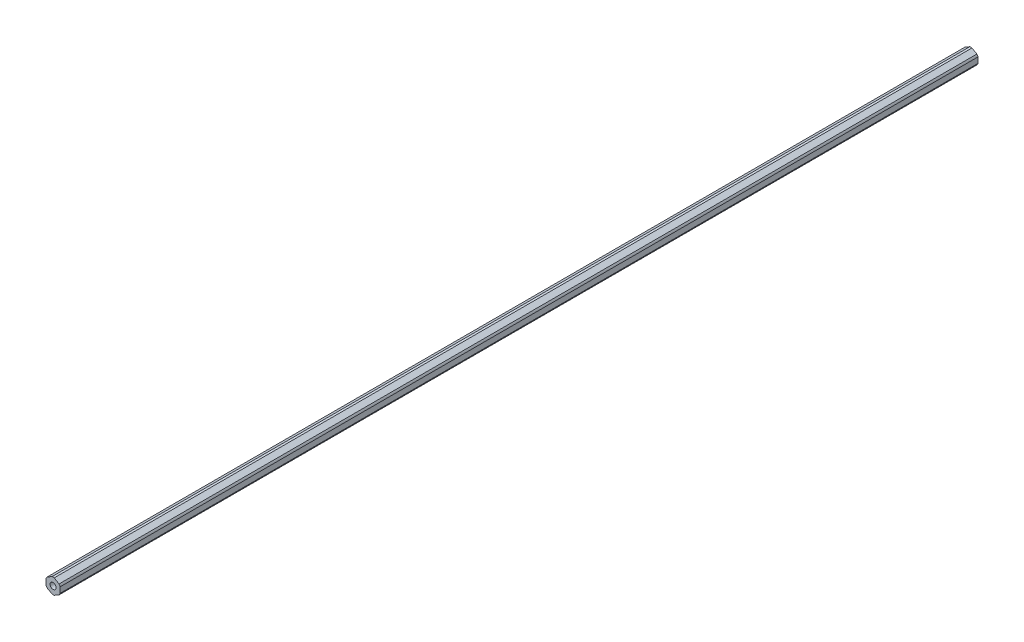
SolidWorks part; units mm, degrees
material "7075-T6 (SN)"
ref_plane "Front Plane" through (0, 0, 0) normal (0, 0, 1) x (1, 0, 0)
ref_plane "Top Plane" through (0, 0, 0) normal (0, 1, 0) x (1, 0, 0)
ref_plane "Right Plane" through (0, 0, 0) normal (1, 0, 0) x (0, 0, -1)
sketch "Sketch2" plane through (0, 0, 0) normal (0, 0, 1) x (1, 0, 0)
  line L1 (0, 5.4993) -> (-4.7625, 2.7496)
  line L2 (-4.7625, 2.7496) -> (-4.7625, -2.7496)
  line L3 (-4.7625, -2.7496) -> (0, -5.4993)
  line L4 (0, -5.4993) -> (4.7625, -2.7496)
  line L5 (4.7625, -2.7496) -> (4.7625, 2.7496)
  line L6 (4.7625, 2.7496) -> (0, 5.4993)
  circle A0 centre (0, 0) radius 4.7625 construction
  circle A3 centre (0, 0) radius 5.125
  dimension "D1" = 9.525
  dimension "D2" = 10.25
extrude "Boss-Extrude1" add sketch "Sketch2" along normal mid plane 615.95 contours L5 A3 L6 L1 L2 L3 L4 region at (0, 0, 0)
hole_wizard "#10-32 Tapped Hole2" positions "3DSketch1" profile "Sketch6" tap size "#10-32" standard "ANSI Inch"
sketch3d "3DSketch1"
  line L0 (0, 0, 307.975) -> (0, 0, -307.975) construction
  point P14 (0, 0, 307.975)
  point P18 (0, 0, -307.975)
sketch "Sketch6" plane through (0, 0, 307.975) normal (1, 0, 0) x (0, -1, 0)
  line L0 (0, 0) -> (0, 17.5608)
  line L1 (0, 17.5608) -> (2.0193, 16.3474)
  line L2 (2.0193, 16.3474) -> (2.0193, 0)
  line L5 (2.0193, 0) -> (0, 0)
  line L10 (0, 17.5608) -> (-2.0193, 16.3474) construction
  line L11 (0, -6.35) -> (0, 107.95) construction
  dimension "Tap Drill Dia." = 4.0386
  dimension "Tap Drill Depth" = 16.3474
  dimension "Drill Angle" = 118
cosmetic thread "Hole Thread2" parameters "D1"=13.97, "D2"=4.826
cosmetic thread "Hole Thread3" parameters "D1"=13.97, "D2"=4.826
equation "\"D2@Sketch2\"=10.25mm"
